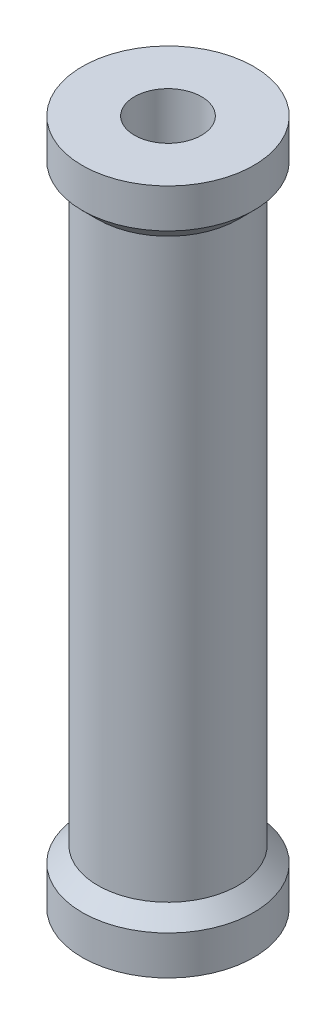
SolidWorks part; units mm, degrees
material "ABS"
ref_plane "前视基准面" through (0, 0, 0) normal (0, 0, 1) x (1, 0, 0)
ref_plane "上视基准面" through (0, 0, 0) normal (0, 1, 0) x (1, 0, 0)
ref_plane "右视基准面" through (0, 0, 0) normal (1, 0, 0) x (0, 0, -1)
other "Configuration Table"
sketch "草图2" plane through (0, 0, 0) normal (0, 1, 0) x (1, 0, 0)
  circle A0 centre (0, 0) radius 2.15
  circle A1 centre (0, 0) radius 4.5
  dimension "D1" = 4.3
  dimension "D2" = 9
extrude "凸台-拉伸1" add sketch "草图2" along normal mid plane 44
sketch "草图3" plane through (0, 22, 0) normal (0, 1, 0) x (1, 0, 0)
  circle A0 centre (0, 0) radius 2.15 construction
  circle A1 centre (0, 0) radius 2.15
  circle A2 centre (0, 0) radius 5.5
  dimension "D1" = 11
extrude "凸台-拉伸2" add sketch "草图3" against normal blind 2
mirror "镜向1" about plane through (0, 0, 0) normal (0, 1, 0) of "凸台-拉伸2"
chamfer "倒角1" distance 1.5 angle 45 2 edges at (0, -20, -4.5) (0, 20, 4.5)
